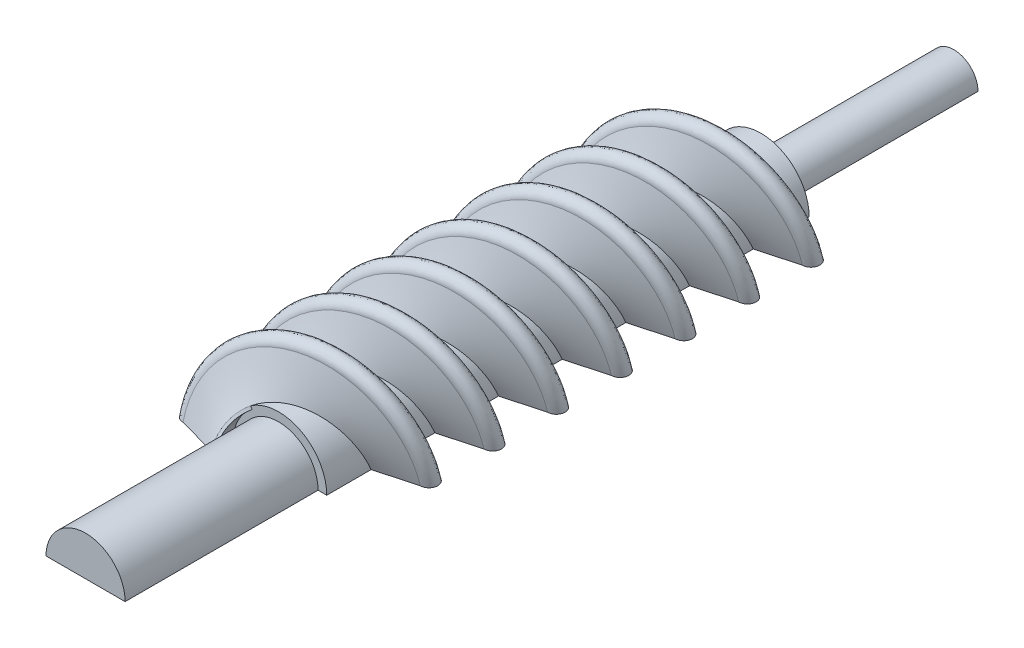
SolidWorks part; units mm, degrees
ref_plane "Plan de face" through (0, 0, 0) normal (0, 0, 1) x (1, 0, 0)
ref_plane "Plan de dessus" through (0, 0, 0) normal (0, 1, 0) x (1, 0, 0)
ref_plane "Plan de droite" through (0, 0, 0) normal (1, 0, 0) x (0, 0, -1)
sketch "Esquisse1" plane through (0, 0, 0) normal (0, 0, 1) x (1, 0, 0)
  circle A0 centre (0, 0) radius 5
  dimension "D1" = 10
extrude "Boss.-Extru.1" add sketch "Esquisse1" along normal blind 50
sketch "Esquisse3" plane through (0, 0, 50) normal (0, 0, 1) x (1, 0, 0)
  circle A0 centre (0, 0) radius 5
curve "Hélice/Spirale1" pitch 13.2 height 46.2 radius 5 centre (0, 0, 50) axis (0, 0, -1) start towards (-1, 0, 0)
sketch "Esquisse4" plane through (0, 0, 0) normal (0, 1, 0) x (1, 0, 0)
  line L0 (-5, -50) -> (-9, -50) construction
  line L1 (-5, 0) -> (-5, -50) construction
  line L2 (-9, -49.1) -> (-5, -48)
  line L3 (-9, -50.9) -> (-5, -52)
  line L5 (-5, -48) -> (-4.702, -48)
  line L6 (-4.702, -48) -> (-4.702, -52)
  line L7 (-4.702, -52) -> (-5, -52)
  arc A1 (-9, -49.1) -> (-9, -50.9) centre (-9, -50) ccw
  spline S0 degree 3 poles (-5, -50) (-5, -49.7265) (-4.7397, -49.1743) (-3.6276, -48.3502) (-1.9632, -47.525) (0, -46.7) (1.9632, -45.875) (3.6276, -45.05) (4.7397, -44.225) (5.1302, -43.4) (4.7397, -42.575) (3.6276, -41.75) (1.4084, -40.65) (-1.4084, -39.55) (-3.6276, -38.45) (-4.7397, -37.625) (-5.1302, -36.8) (-4.7397, -35.975) (-3.6276, -35.15) (-1.4084, -34.05) (1.4084, -32.95) (3.6276, -31.85) (4.7397, -31.025) (5.1302, -30.2) (4.7397, -29.375) (3.6276, -28.55) (1.4084, -27.45) (-1.4084, -26.35) (-3.6276, -25.25) (-4.7397, -24.425) (-5.1302, -23.6) (-4.7397, -22.775) (-3.6276, -21.95) (-1.4084, -20.85) (1.4084, -19.75) (3.6276, -18.65) (4.7397, -17.825) (5.1302, -17) (4.7397, -16.175) (3.6276, -15.35) (1.4084, -14.25) (-1.4084, -13.15) (-3.6276, -12.05) (-4.7397, -11.225) (-5.1302, -10.4) (-4.7397, -9.575) (-3.6276, -8.75) (-1.9632, -7.925) (0, -7.1) (1.9632, -6.275) (3.6276, -5.4498) (4.7397, -4.6257) (5, -4.0735) (5, -3.8) knots 0 0 0 0 0.017857 0.035714 0.053571 0.071429 0.089286 0.107143 0.125 0.142857 0.160714 0.178571 0.196429 0.232143 0.25 0.267857 0.285714 0.303571 0.321429 0.339286 0.375 0.392857 0.410714 0.428571 0.446429 0.464286 0.482143 0.517857 0.535714 0.553571 0.571429 0.589286 0.607143 0.625 0.660714 0.678571 0.696429 0.714286 0.732143 0.75 0.767857 0.803571 0.821429 0.839286 0.857143 0.875 0.892857 0.910714 0.928571 0.946429 0.964286 0.982143 1 1 1 1 construction
  dimension "D3" = 0.9
  dimension "D1" = 4
  dimension "D2" = 4
sweep "Balayage2" add profiles "Esquisse4" path "Hélice/Spirale1"
pattern_circular "CirPattern1" count 2 over 360 about axis through (0, 0, 50) along (0, 0, -1) of "Balayage2"
sketch "arbre" plane through (0, 0, 0) normal (0, 0, -1) x (-1, 0, 0)
  circle A0 centre (0, 0) radius 2.5
extrude "Boss.-Extru.3" add sketch "arbre" along normal blind 20 and the other way blind 70
sketch "Esquisse8" plane through (0, 0, 70) normal (0, 0, 1) x (1, 0, 0)
  circle A0 centre (0, 0) radius 4.1
extrude "Boss.-Extru.4" add sketch "Esquisse8" against normal blind 20
sketch "Sketch1" plane through (0, 0, 70) normal (0, 0, 1) x (1, 0, 0)
  line L1 (0, 0) -> (14.8915, 0)
  line L3 (0, -11.3591) -> (14.8915, -11.3591)
  line L4 (14.8915, 0) -> (14.8915, -11.3591)
  line L5 (0, 0) -> (-12.0288, 0)
  line L7 (0, -11.3591) -> (-12.0288, -11.3591)
  line L8 (-12.0288, 0) -> (-12.0288, -11.3591)
extrude "Cut-Extrude1" cut sketch "Sketch1" against normal through all
